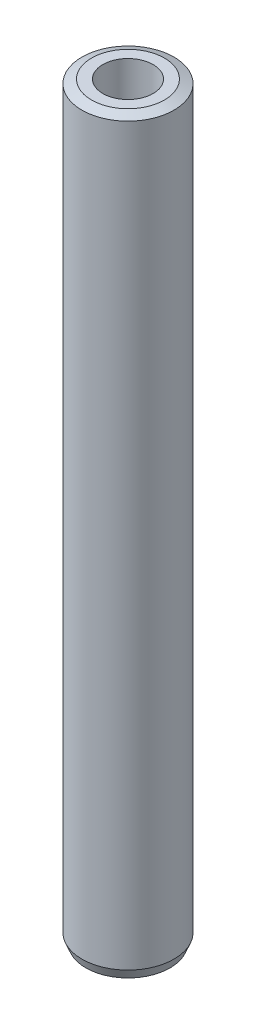
SolidWorks part; units mm, degrees
ref_plane "Front Plane" through (0, 0, 0) normal (0, 0, 1) x (1, 0, 0)
ref_plane "Top Plane" through (0, 0, 0) normal (0, 1, 0) x (1, 0, 0)
ref_plane "Right Plane" through (0, 0, 0) normal (1, 0, 0) x (0, 0, -1)
sketch "Sketch1" plane through (0, 0, 0) normal (0, 1, 0) x (1, 0, 0)
  circle A0 centre (0, 0) radius 12.5
  dimension "SHAFT_OD" = 25
extrude "Boss-Extrude1" add sketch "Sketch1" along normal blind 203.2898
sketch "Sketch2" plane through (0, 0, 0) normal (0, 1, 0) x (1, 0, 0)
  circle A0 centre (0, 0) radius 6.827
  dimension "BORE_D" = 13.654
extrude "Cut-Extrude1" cut sketch "Sketch2" along normal through all
chamfer "Chamfer1" distance 1.0724 angle 67.688 2 edges at (0, 203.2898, 12.5) (0, 0, 12.5) first distance on face at (0, 203.2898, 12.5) first distance on face at (0, 0, 6.827)
